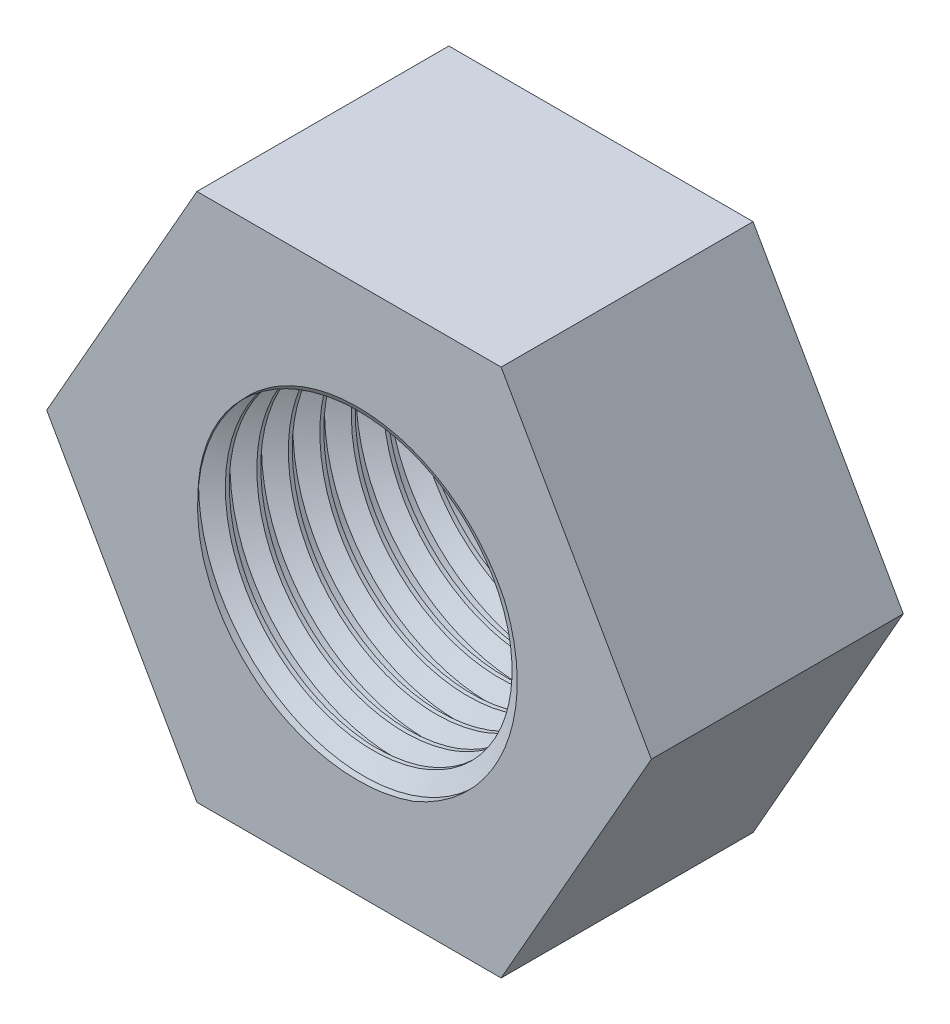
SolidWorks part; units mm, degrees
material "Ductile Iron"
ref_plane "Front Plane" through (0, 0, 0) normal (0, 0, 1) x (1, 0, 0)
ref_plane "Top Plane" through (0, 0, 0) normal (0, 1, 0) x (1, 0, 0)
ref_plane "Right Plane" through (0, 0, 0) normal (1, 0, 0) x (0, 0, -1)
sketch "Sketch1" plane through (0, 0, 0) normal (0, 0, 1) x (1, 0, 0)
  line L0 (0, 0) -> (-12369.8203, 0) construction
  line L1 (0, 0) -> (0, 12369.8203) construction
  line L3 (-12, 0) -> (-6.0374, -10.5)
  line L4 (-6.0374, -10.5) -> (6.0374, -10.5)
  line L5 (6.0374, -10.5) -> (12, 0)
  line L6 (12, 0) -> (6.0374, 10.5)
  line L7 (6.0374, 10.5) -> (-6.0374, 10.5)
  line L8 (-6.0374, 10.5) -> (-12, 0)
  circle A0 centre (0, 0) radius 6
  point P14 (0, 10.5)
  dimension "D3" = 12
  dimension "D1" = 24
  dimension "D2" = 21
extrude "Boss-Extrude1" add sketch "Sketch1" along normal blind 10
thread "Thread1" pitch 1.25 method cut profile "Thread Profile1" start angle 0, offset 10, length 25, pitch 1.25, diameter 12
ref_plane "Plane1" through (-6, 0, 20) normal (0, 1, 0) x (1, 0, 0)
sketch "Thread Profile1" plane through (-6, 0, 20) normal (0, 1, 0) x (1, 0, 0)
  line L0 (0, 0) -> (0, 1.25) construction
  line L11 (0, 0) -> (0, 1.0937)
  line L12 (0, 1.0937) -> (-0.6766, 0.7031)
  line L13 (-0.6766, 0.7031) -> (-0.6766, 0.3906)
  line L15 (-0.6766, 0.3906) -> (0, 0)
  line L17 (-0.6766, 0.5469) -> (0, 0.5469) construction
  point P2 (0, 0)
  dimension "Pitch" = 1.25
  dimension "Profile_Angle" = 60
  dimension "Profile_Land" = 0.3125
  dimension "Profile_Height" = 0.6766
